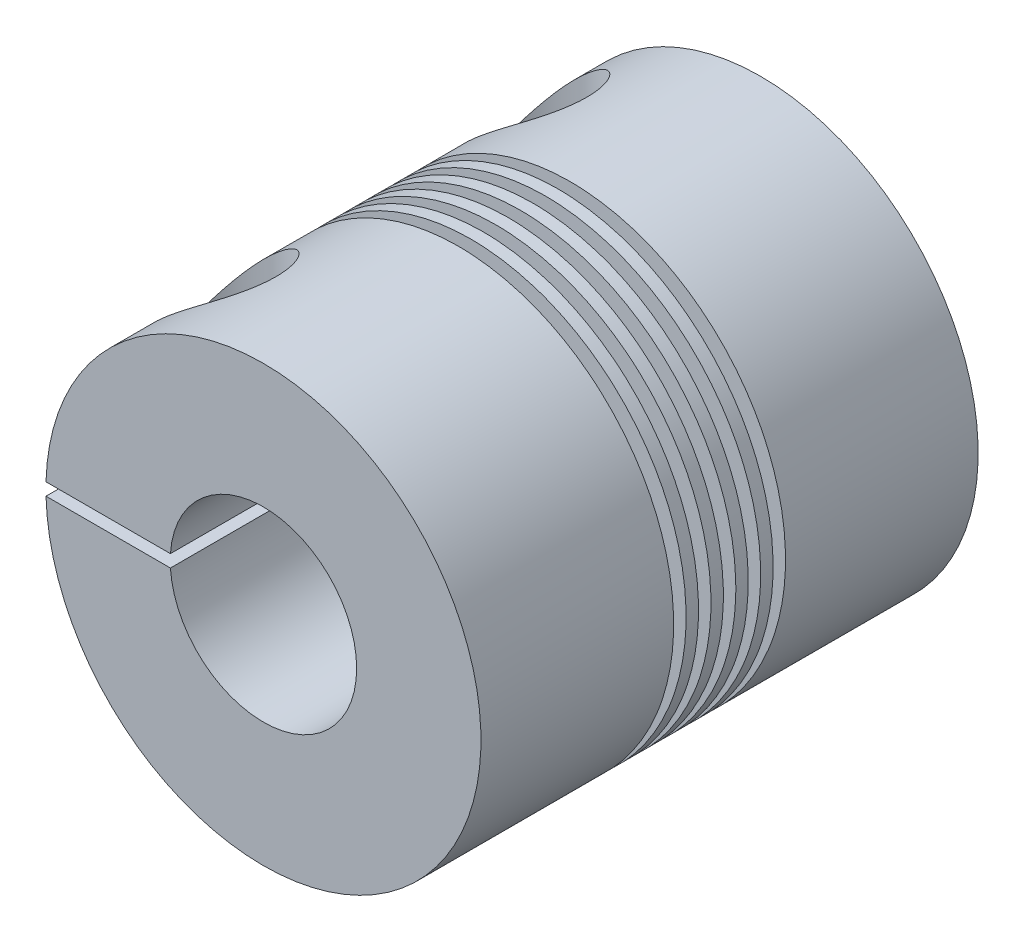
SolidWorks part; units mm, degrees
material "Acero al carbono fundido"
ref_plane "Alzado" through (0, 0, 0) normal (0, 0, 1) x (1, 0, 0)
ref_plane "Planta" through (0, 0, 0) normal (0, 1, 0) x (1, 0, 0)
ref_plane "Vista lateral" through (0, 0, 0) normal (1, 0, 0) x (0, 0, -1)
sketch "Croquis1" plane through (0, 0, 0) normal (0, 0, 1) x (1, 0, 0)
  circle A0 centre (0, 0) radius 17.5
  dimension "D1" = 35
extrude "Saliente-Extruir1" add sketch "Croquis1" along normal blind 40
ref_plane "Plano2" through (0, 0, 15) normal (0, 0, 1) x (1, 0, 0)
sketch "Croquis4" plane through (0, 0, 15) normal (0, 0, 1) x (1, 0, 0)
  circle A0 centre (0, 0) radius 17.5 construction
  circle A1 centre (0, 0) radius 17.5
curve "Hélice/Espiral1" pitch 2 height 10 radius 17.5 left hand yes centre (0, 0, 15) axis (0, 0, 1) start towards (-1, 0, 0)
ref_plane "Plano3" through (0, 0, 0) normal (0, 1, 0) x (1, 0, 0)
sketch "Croquis7" plane through (0, 0, 0) normal (0, 1, 0) x (1, 0, 0)
  line L0 (-17.5, -14.5) -> (-17.5, -15.5)
  line L1 (-17.5, 0) -> (-17.5, -40) construction
  line L2 (-17.5, -15.5) -> (-9.5, -15.5)
  line L3 (-9.5, -15.5) -> (-9.5, -14.5)
  line L4 (-9.5, -14.5) -> (-17.5, -14.5)
  spline S0 degree 3 poles (-17.5, -15) (-17.5, -15.0361) (-16.8132, -15.1088) (-13.8413, -15.2174) (-9.2712, -15.3261) (-3.6304, -15.4348) (2.4297, -15.5435) (8.2091, -15.6522) (13.0406, -15.7609) (16.3662, -15.8696) (17.8018, -15.9783) (17.1817, -16.087) (14.5775, -16.1957) (10.2899, -16.3043) (4.8141, -16.413) (-1.2177, -16.5217) (-7.1088, -16.6304) (-12.1791, -16.7391) (-15.8429, -16.8478) (-17.6772, -16.9565) (-17.4702, -17.0652) (-15.2458, -17.1739) (-11.2608, -17.2826) (-5.9754, -17.3913) (0, -17.5) (5.9754, -17.6087) (11.2608, -17.7174) (15.2458, -17.8261) (17.4702, -17.9348) (17.6772, -18.0435) (15.8429, -18.1522) (12.1791, -18.2609) (7.1088, -18.3696) (1.2177, -18.4783) (-4.8141, -18.587) (-10.2899, -18.6957) (-14.5775, -18.8043) (-17.1817, -18.913) (-17.8018, -19.0217) (-16.3662, -19.1304) (-13.0406, -19.2391) (-8.2091, -19.3478) (-2.4297, -19.4565) (3.6304, -19.5652) (9.2712, -19.6739) (13.8413, -19.7826) (16.8132, -19.8913) (17.8434, -20) (16.8132, -20.1087) (13.8413, -20.2174) (9.2712, -20.3261) (3.6304, -20.4348) (-2.4297, -20.5435) (-8.2091, -20.6522) (-13.0406, -20.7609) (-16.3662, -20.8696) (-17.8018, -20.9783) (-17.1817, -21.087) (-14.5775, -21.1957) (-10.2899, -21.3043) (-4.8141, -21.413) (1.2177, -21.5217) (7.1088, -21.6304) (12.1791, -21.7391) (15.8429, -21.8478) (17.6772, -21.9565) (17.4702, -22.0652) (15.2458, -22.1739) (11.2608, -22.2826) (5.9754, -22.3913) (0, -22.5) (-5.9754, -22.6087) (-11.2608, -22.7174) (-15.2458, -22.8261) (-17.4702, -22.9348) (-17.6772, -23.0435) (-15.8429, -23.1522) (-12.1791, -23.2609) (-7.1088, -23.3696) (-1.2177, -23.4783) (4.8141, -23.587) (10.2899, -23.6957) (14.5775, -23.8043) (17.1817, -23.913) (17.8018, -24.0217) (16.3662, -24.1304) (13.0406, -24.2391) (8.2091, -24.3478) (2.4297, -24.4565) (-3.6304, -24.5652) (-9.2712, -24.6739) (-13.8413, -24.7826) (-16.8132, -24.8912) (-17.5, -24.9639) (-17.5, -25) knots 0 0 0 0 0.01087 0.021739 0.032609 0.043478 0.054348 0.065217 0.076087 0.086957 0.097826 0.108696 0.119565 0.130435 0.141304 0.152174 0.163043 0.173913 0.184783 0.195652 0.206522 0.217391 0.228261 0.23913 0.25 0.26087 0.271739 0.282609 0.293478 0.304348 0.315217 0.326087 0.336957 0.347826 0.358696 0.369565 0.380435 0.391304 0.402174 0.413043 0.423913 0.434783 0.445652 0.456522 0.467391 0.478261 0.48913 0.5 0.51087 0.521739 0.532609 0.543478 0.554348 0.565217 0.576087 0.586957 0.597826 0.608696 0.619565 0.630435 0.641304 0.652174 0.663043 0.673913 0.684783 0.695652 0.706522 0.717391 0.728261 0.73913 0.75 0.76087 0.771739 0.782609 0.793478 0.804348 0.815217 0.826087 0.836957 0.847826 0.858696 0.869565 0.880435 0.891304 0.902174 0.913043 0.923913 0.934783 0.945652 0.956522 0.967391 0.978261 0.98913 1 1 1 1 construction
  point P4 (-17.5, -15)
  dimension "D1" = 1
  dimension "D2" = 8
sweep "Cortar-Barrer2" cut profiles "Croquis7" path "Hélice/Espiral1" align with end faces yes
sketch "Croquis8" plane through (0, 0, 40) normal (0, 0, 1) x (1, 0, 0)
  circle A0 centre (0, 0) radius 7.5
  dimension "D1" = 15
extrude "Cortar-Extruir1" cut sketch "Croquis8" against normal blind 15
sketch "Croquis9" plane through (0, 0, 0) normal (0, 0, -1) x (-1, 0, 0)
  circle A0 centre (0, 0) radius 5
  dimension "D1" = 10
extrude "Cortar-Extruir2" cut sketch "Croquis9" against normal blind 15
sketch "Croquis13" plane through (0, 0, 0) normal (1, 0, 0) x (0, 0, -1)
  line L0 (0, 0.5) -> (-13, 0.5)
  line L1 (-13, 0.5) -> (-13, -0.5)
  line L2 (-13, -0.5) -> (0, -0.5)
  line L3 (0, -0.5) -> (0, 0.5)
  line L4 (-40, 0.5) -> (-27, 0.5)
  line L5 (-27, 0.5) -> (-27, -0.5)
  line L6 (-27, -0.5) -> (-40, -0.5)
  line L7 (-40, -0.5) -> (-40, 0.5)
  line L10 (0, 0) -> (-40, 0) construction
  line L11 (19.25, 0) -> (-19.25, 0) construction
  line L12 (-40, 17.5) -> (-40, -17.5) construction
  point P10 (0, 0)
  point P14 (-40, 0)
  point P15 (0, 0)
  point P16 (0, 0)
  dimension "D1" = 13
  dimension "D2" = 1
extrude "Cortar-Extruir3" cut sketch "Croquis13" against normal blind 28
ref_plane "Plano4" through (0, 17.5, 0) normal (0, 1, 0) x (1, 0, 0)
hole_wizard "Refrentado para tornillo con cabeza troncocónica de M42" positions "Croquis22" profile "Croquis23" counterbore size "M4" standard "Ansi Metric" end condition through all
sketch "Croquis22" plane through (0, 17.5, 0) normal (0, 1, 0) x (1, 0, 0)
  line L0 (-11.4929, -32) -> (-11.4929, -7) construction
  line L2 (-17.4929, -40) -> (17.5, -40) construction
  line L3 (-17.4929, -40) -> (-17.4929, -27) construction
  point P0 (-11.4929, -32)
  point P2 (-11.4929, -7)
  dimension "D1" = 25
  dimension "D2" = 8
  dimension "D3" = 6
sketch "Croquis23" plane through (-11.4929, 17.5, 32) normal (1, 0, 0) x (0, 0, 1)
  line L0 (0, 0) -> (0, 35.9006)
  line L1 (0, 35.9006) -> (2.25, 35.9006)
  line L3 (2.25, 35.9006) -> (2.25, 11)
  line L4 (4.5, 11) -> (2.25, 11)
  line L5 (4.5, 11) -> (4.5, 0.025)
  line L6 (4.5, 0.025) -> (4.525, 0)
  line L7 (4.525, 0) -> (0, 0)
  line L8 (-4.5, 0.025) -> (-4.525, 0) construction
  line L11 (0, -6.35) -> (0, 107.95) construction
  dimension "Diámetro de taladro hasta el siguiente" = 4.5
  dimension "Profundidad de taladro hasta el siguiente" = 35.9006
  dimension "Diámetro de refrentado" = 9
  dimension "Profundidad de refrentado" = 11
  dimension "Diámetro de avellanado cercano" = 9.05
  dimension "Ángulo de avellanado cercano" = 90
